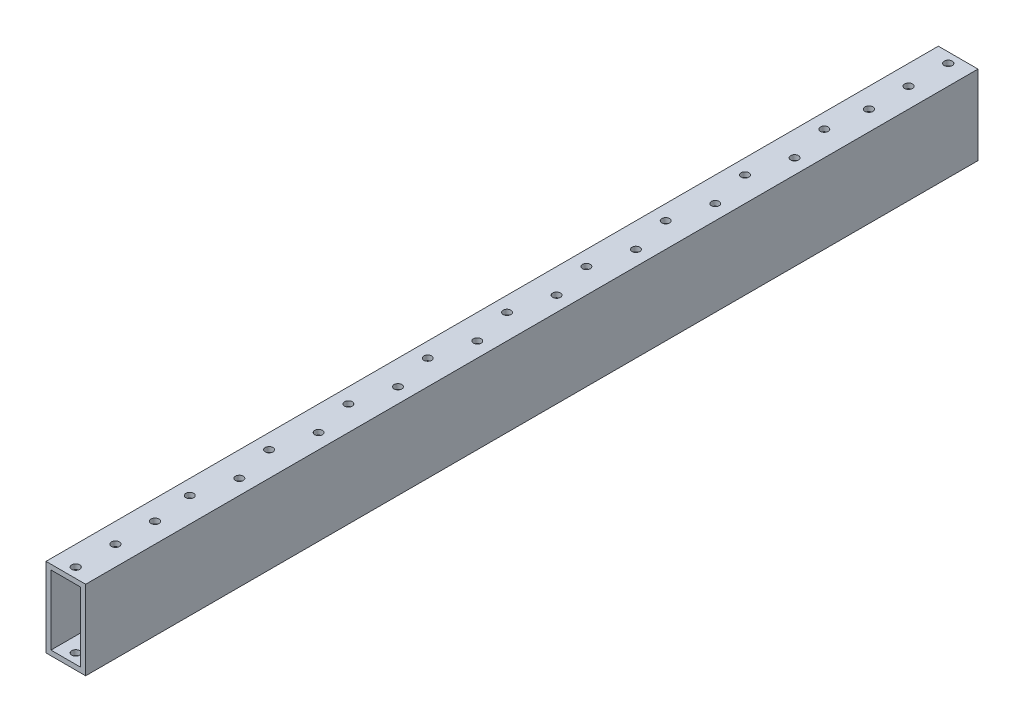
SolidWorks part; units mm, degrees
material "6061-T6 (SS)"
ref_plane "Front Plane" through (0, 0, 0) normal (0, 0, 1) x (1, 0, 0)
ref_plane "Top Plane" through (0, 0, 0) normal (0, 1, 0) x (1, 0, 0)
ref_plane "Right Plane" through (0, 0, 0) normal (1, 0, 0) x (0, 0, -1)
sketch "Sketch1" plane through (0, 0, 0) normal (0, 0, 1) x (1, 0, 0)
  line L1 (-12.7, -25.4) -> (12.7, -25.4)
  line L2 (-12.7, -25.4) -> (-12.7, 25.4)
  line L3 (-12.7, 25.4) -> (12.7, 25.4)
  line L4 (12.7, -25.4) -> (12.7, 25.4)
  line L5 (-12.7, -25.4) -> (12.7, 25.4) construction
  line L6 (-12.7, 25.4) -> (12.7, -25.4) construction
  point P0 (0, 0)
  dimension "D1" = 50.8
  dimension "D2" = 25.4
extrude "Extrude-Thin1" add sketch "Sketch1" along normal blind 571.5 thin thin type one direction reverse wall 3.175
hole_wizard "#10 Clearance Hole1" positions "3DSketch1" profile "Sketch3" hole size "#10" standard "ANSI Inch" end condition through all
sketch3d "3DSketch1"
  line L1 (12.7, 25.4, 0) -> (-12.7, 25.4, 0) construction
  line L6 (0, 25.4, 571.5) -> (0, 25.4, 0) construction
  line L7 (12.7, 25.4, 571.5) -> (-12.7, 25.4, 571.5) construction
  point P57 (0, 25.4, 6.35)
  point P59 (0, 25.4, 31.75)
  point P61 (0, 25.4, 57.15)
  point P63 (0, 25.4, 539.75)
  point P65 (0, 25.4, 514.35)
  point P67 (0, 25.4, 565.15)
  dimension "D1" = 25.4
  dimension "D2" = 25.4
  dimension "D3" = 6.35
  dimension "D4" = 25.4
  dimension "D5" = 25.4
  dimension "D6" = 6.35
sketch "Sketch3" plane through (0, 25.4, 565.15) normal (1, 0, 0) x (0, 0, 1)
  line L0 (0, 0) -> (0, 50.8)
  line L1 (0, 50.8) -> (2.5527, 50.8)
  line L2 (2.5527, 50.8) -> (2.5527, 0)
  line L5 (2.5527, 0) -> (0, 0)
  line L11 (0, -6.35) -> (0, 107.95) construction
  dimension "Thru Hole Dia." = 5.1054
  dimension "Thru Hole Depth" = 50.8
hole_wizard "3/16 (0.195) Diameter Hole1" positions "Sketch4" profile "Sketch5" hole size "3/16" standard "ANSI Inch" end condition up to next
sketch "Sketch4" plane through (0, 25.4, 0) normal (0, 1, 0) x (1, 0, 0)
  point P145 (-3.1807, -82.55)
  point P148 (3.1693, -107.95)
  point P151 (-3.1807, -133.35)
  point P154 (3.1693, -158.75)
  point P157 (-3.1807, -184.15)
  point P160 (3.1693, -209.55)
  point P163 (-3.1807, -234.95)
  point P166 (3.1693, -260.35)
  point P169 (-3.1807, -285.75)
  point P172 (3.1693, -311.15)
  point P175 (-3.1807, -336.55)
  point P178 (3.1693, -361.95)
  point P181 (-3.1807, -387.35)
  point P184 (3.1693, -412.75)
  point P187 (-3.1807, -438.15)
  point P190 (3.1693, -463.55)
  point P193 (-3.1807, -488.95)
sketch "Sketch5" plane through (-3.1807, 25.4, 82.55) normal (1, 0, 0) x (0, 0, 1)
  line L0 (0, 0) -> (0, 3.175)
  line L1 (0, 3.175) -> (2.4765, 3.175)
  line L2 (2.4765, 3.175) -> (2.4765, 0)
  line L5 (2.4765, 0) -> (0, 0)
  line L11 (0, -6.35) -> (0, 107.95) construction
  dimension "Thru Hole Dia." = 4.953
  dimension "Thru Hole Depth" = 3.175
hole_wizard "3/16 (0.195) Diameter Hole2" positions "Sketch6" profile "Sketch7" hole size "3/16" standard "ANSI Inch"
sketch "Sketch6" plane through (0, -25.4, 0) normal (0, -1, 0) x (-1, 0, 0)
  point P23 (0.0807, -226.187)
  point P26 (0.0807, -251.587)
  point P29 (0.0807, -276.987)
  point P32 (0.0807, -302.387)
  point P35 (0.0807, -327.787)
  point P38 (0.0807, -353.187)
sketch "Sketch7" plane through (-0.0807, -25.4, 226.187) normal (1, 0, 0) x (0, 0, -1)
  line L0 (0, 0) -> (0, 4.663)
  line L1 (0, 4.663) -> (2.4765, 3.175)
  line L2 (2.4765, 3.175) -> (2.4765, 0)
  line L5 (2.4765, 0) -> (0, 0)
  line L10 (0, 4.663) -> (-2.4765, 3.175) construction
  line L11 (0, -6.35) -> (0, 107.95) construction
  dimension "Hole Dia." = 4.953
  dimension "Hole Depth" = 3.175
  dimension "Drill Angle" = 118
